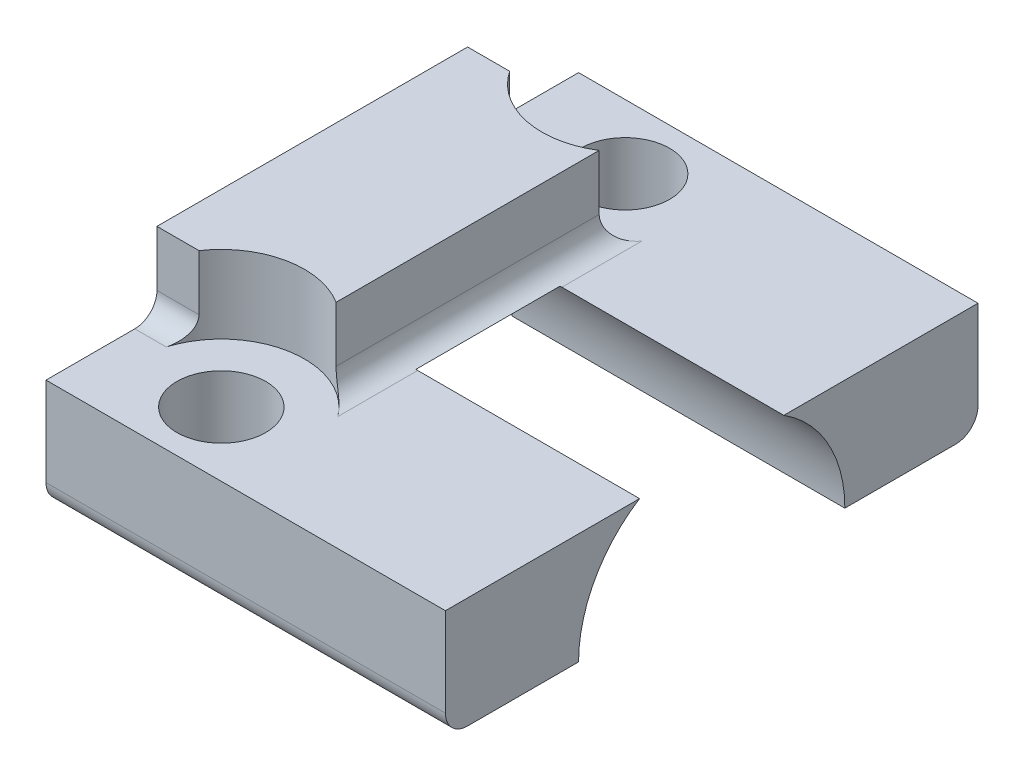
SolidWorks part; units mm, degrees
ref_plane "前基準面" through (0, 0, 0) normal (0, 0, 1) x (1, 0, 0)
ref_plane "上基準面" through (0, 0, 0) normal (0, 1, 0) x (1, 0, 0)
ref_plane "右基準面" through (0, 0, 0) normal (1, 0, 0) x (0, 0, -1)
sketch "草圖1" plane through (0, 0, 0) normal (1, 0, 0) x (0, 0, -1)
  line L0 (-3.2453, 2.1203) -> (3.2453, 2.1203)
  line L1 (-12, -2.8829) -> (-6.0005, -2.8829)
  line L2 (-12, -2.8829) -> (-12, 2.1171)
  line L3 (-7, 5.6171) -> (7, 5.6171)
  line L4 (12, -2.8829) -> (12, 2.1171)
  line L5 (6.0005, -2.8829) -> (12, -2.8829)
  line L6 (0, -1000) -> (0, 49000) construction
  line L7 (-12, 2.1171) -> (-7, 2.1171)
  line L8 (-7, 2.1171) -> (-7, 5.6171)
  line L13 (12, 2.1171) -> (7, 2.1171)
  line L14 (7, 2.1171) -> (7, 5.6171)
  arc A0 (-6.0005, -2.8829) -> (-3.2453, 2.1203) centre (-0.08, -2.8829) cw
  arc A1 (6.0005, -2.8829) -> (3.2453, 2.1203) centre (0.08, -2.8829) ccw
  dimension "D4" = 5.9205
  dimension "D2" = 0.16
  dimension "D3" = 8.5
  dimension "D6" = 3.5
  dimension "D7" = 24
  dimension "D9" = 2.1203
  dimension "D10" = 5.6171
  dimension "D11" = 14
extrude "填料-伸長1" add sketch "草圖1" along normal blind 13 and the other way blind 5
sketch "草圖3" plane through (0, 2.1171, 0) normal (0, 1, 0) x (1, 0, 0)
  line L0 (-1000, 0) -> (49000, 0) construction
  circle A0 centre (0, 9.1) radius 2
  circle A1 centre (0, -9.1) radius 2
  dimension "D1" = 4
  dimension "D3" = 18.2
extrude "除料-伸長1" cut sketch "草圖3" against normal up to next
sketch "草圖6" plane through (13, 0, 0) normal (1, 0, 0) x (0, 0, -1)
  line L0 (7, 5.6171) -> (-7, 5.6171) construction
  line L1 (-7, 5.6171) -> (7, 5.6171)
  line L2 (-7, 5.6171) -> (-7, 2.1171)
  line L3 (-7, 2.1171) -> (7, 2.1171)
  line L4 (7, 5.6171) -> (7, 2.1171)
  line L5 (-7, 5.6171) -> (-7, 2.1171) construction
  line L6 (7, 2.1171) -> (7, 5.6171) construction
  dimension "D1" = 3.5
extrude "除料-伸長2" cut sketch "草圖6" against normal blind 11
sketch "草圖7" plane through (-5, 0, 0) normal (-1, 0, 0) x (0, 0, 1)
  line L1 (-6.2214, 2.3303) -> (6.2214, 2.3303)
  line L2 (-6.2214, 2.3303) -> (-6.2214, -8.0962)
  line L3 (-6.2214, -8.0962) -> (6.2214, -8.0962)
  line L4 (6.2214, 2.3303) -> (6.2214, -8.0962)
  line L5 (-6.2214, 2.3303) -> (6.2214, -8.0962) construction
  line L6 (-6.2214, -8.0962) -> (6.2214, 2.3303) construction
  point P0 (0, -2.8829)
extrude "除料-伸長3" cut sketch "草圖7" against normal blind 3
fillet "圓角2" radius 1 6 edges at (-3.5, 2.3303, -6.2214) (-3.5, 2.3303, 6.2214) (-1.5, 2.1171, 7) (-1.5, 2.1171, -7) (4, -2.8829, 12) (4, -2.8829, -12)
sketch "草圖9" plane through (0, 5.6171, 0) normal (0, 1, 0) x (1, 0, 0)
  circle A0 centre (0, 9.1) radius 3.75
  circle A1 centre (0, -9.1) radius 3.75
  dimension "D1" = 7.5
extrude "除料-伸長5" cut sketch "草圖9" against normal blind 3.5
fillet "圓角3" radius 1 1 edges at (2, 2.1171, 4.5892)
